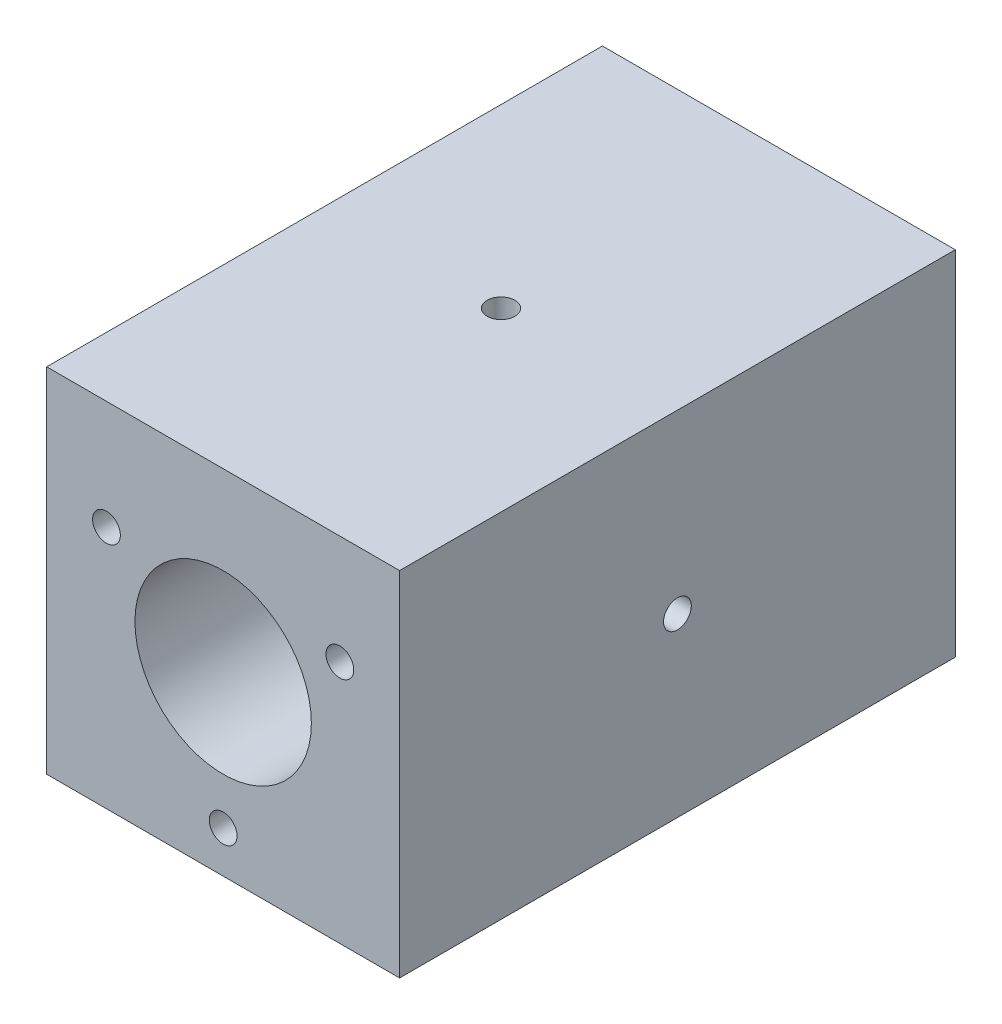
SolidWorks part; units mm, degrees
material "6061-T6 (SS)"
ref_plane "Front Plane" through (0, 0, 0) normal (0, 0, 1) x (1, 0, 0)
ref_plane "Top Plane" through (0, 0, 0) normal (0, 1, 0) x (1, 0, 0)
ref_plane "Right Plane" through (0, 0, 0) normal (1, 0, 0) x (0, 0, -1)
sketch "Sketch1" plane through (0, 0, 0) normal (0, 0, 1) x (1, 0, 0)
  line L1 (15.875, 15.875) -> (-15.875, 15.875)
  line L2 (15.875, 15.875) -> (15.875, -15.875)
  line L3 (15.875, -15.875) -> (-15.875, -15.875)
  line L4 (-15.875, 15.875) -> (-15.875, -15.875)
  line L5 (15.875, 15.875) -> (-15.875, -15.875) construction
  line L6 (15.875, -15.875) -> (-15.875, 15.875) construction
  circle A0 centre (0, 0) radius 7.9375
  circle A1 centre (-10.5, 6.0622) radius 1.25
  circle A2 centre (10.5, 6.0622) radius 1.25
  circle A3 centre (0, -12.1244) radius 1.25
  point P0 (0, 0)
  point P16 (0, 0)
  dimension "D2" = 15.875
  dimension "D3" = 2.5
  dimension "D1" = 31.75
  dimension "D5" = 21
  dimension "D4" = 3
extrude "Boss-Extrude1" add sketch "Sketch1" along normal mid plane 50
sketch "Sketch2" plane through (0, 15.875, 0) normal (0, 1, 0) x (1, 0, 0)
  point P0 (0, 0)
hole_wizard "M3x0.5 Tapped Hole1" positions "Sketch2" profile "Sketch3" tap size "M3x0.5" standard "ANSI Metric" end condition up to next
sketch "Sketch3" plane through (0, 15.875, 0) normal (1, 0, 0) x (0, 0, 1)
  line L0 (0, 0) -> (0, 7.9375)
  line L1 (0, 7.9375) -> (1.25, 7.9375)
  line L2 (1.25, 7.9375) -> (1.25, 0)
  line L5 (1.25, 0) -> (0, 0)
  line L11 (0, -6.35) -> (0, 107.95) construction
  dimension "Thru Tap Drill Dia." = 2.5
  dimension "Thru Tap Drill Depth" = 7.9375
cosmetic thread "Hole Thread1" parameters "D2"=3
sketch "Sketch4" plane through (15.875, 0, 0) normal (1, 0, 0) x (0, 0, -1)
  point P0 (0, 0)
hole_wizard "M3x0.5 Tapped Hole2" positions "Sketch4" profile "Sketch5" tap size "M3x0.5" standard "ANSI Metric" end condition up to next
sketch "Sketch5" plane through (15.875, 0, 0) normal (0, 1, 0) x (0, 0, -1)
  line L0 (0, 0) -> (0, 7.9375)
  line L1 (0, 7.9375) -> (1.25, 7.9375)
  line L2 (1.25, 7.9375) -> (1.25, 0)
  line L5 (1.25, 0) -> (0, 0)
  line L11 (0, -6.35) -> (0, 107.95) construction
  dimension "Thru Tap Drill Dia." = 2.5
  dimension "Thru Tap Drill Depth" = 7.9375
cosmetic thread "Hole Thread2" parameters "D2"=3
